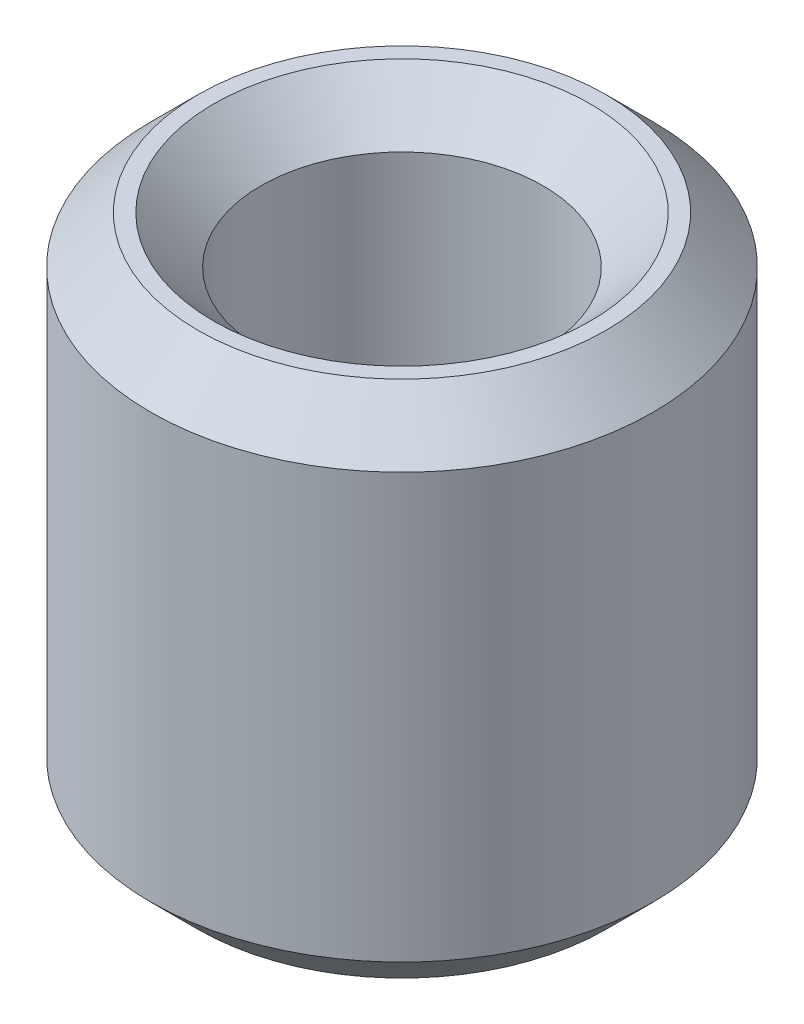
SolidWorks part; units mm, degrees
ref_plane "Front Plane" through (0, 0, 0) normal (0, 0, 1) x (1, 0, 0)
ref_plane "Top Plane" through (0, 0, 0) normal (0, 1, 0) x (1, 0, 0)
ref_plane "Right Plane" through (0, 0, 0) normal (1, 0, 0) x (0, 0, -1)
sketch "Sketch1" plane through (0, 0, 0) normal (0, 1, 0) x (1, 0, 0)
  circle A0 centre (0, 0) radius 17.5
  dimension "SLEEVE_OD" = 35
extrude "Boss-Extrude1" add sketch "Sketch1" along normal blind 36.1169
sketch "Sketch2" plane through (0, 0, 0) normal (0, 1, 0) x (1, 0, 0)
  circle A0 centre (0, 0) radius 9.817
  dimension "BORE_D" = 19.634
extrude "Cut-Extrude1" cut sketch "Sketch2" along normal through all
chamfer "Chamfer1" distance 3.2898 angle 45 4 edges at (0, 36.1169, 9.817) (0, 0, 9.817) (0, 0, 17.5) (0, 36.1169, 17.5)
